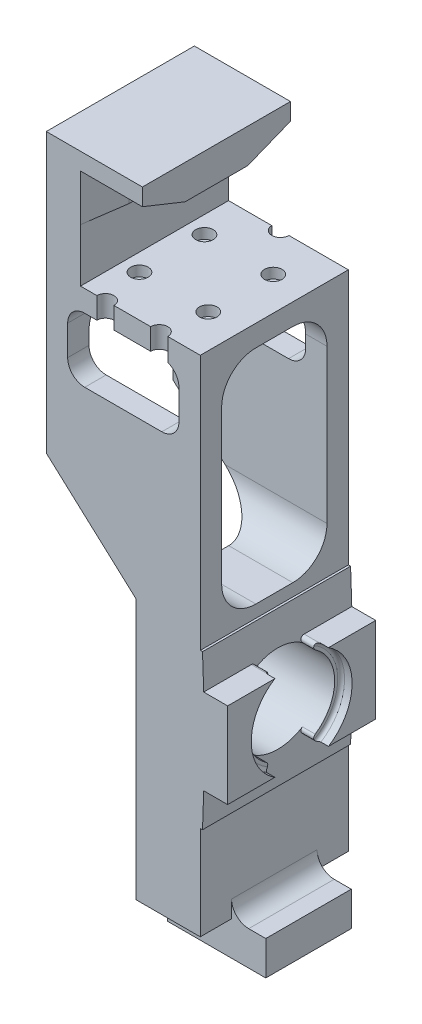
SolidWorks part; units mm, degrees
ref_plane "Front Plane" through (0, 0, 0) normal (0, 0, 1) x (1, 0, 0)
ref_plane "Top Plane" through (0, 0, 0) normal (0, 1, 0) x (1, 0, 0)
ref_plane "Right Plane" through (0, 0, 0) normal (1, 0, 0) x (0, 0, -1)
sketch "Sketch1" plane through (0, 0, 0) normal (0, 0, 1) x (1, 0, 0)
  line L0 (-19.75, 28.514) -> (-19.75, 29.784)
  line L1 (-12.7, 12.7) -> (12.7, 12.7)
  line L2 (-12.7, 12.7) -> (-12.7, -12.7)
  line L3 (-12.7, -12.7) -> (12.7, -12.7)
  line L4 (12.7, 12.7) -> (12.7, -12.7)
  line L5 (-12.7, 12.7) -> (12.7, -12.7) construction
  line L6 (-12.7, -12.7) -> (12.7, 12.7) construction
  line L7 (-21, 30.5968) -> (21, 30.5968)
  line L8 (-21, 30.5968) -> (-21, 29.784)
  line L9 (-21, 29.784) -> (21, 29.784)
  line L10 (21, 30.5968) -> (21, 29.784)
  line L11 (-21, 30.5968) -> (21, 29.784) construction
  line L12 (-21, 29.784) -> (21, 30.5968) construction
  line L13 (-21.6, 28.514) -> (-13.9, 28.514)
  line L14 (-21.6, 28.514) -> (-21.6, 24.714)
  line L15 (-21.6, 24.714) -> (-13.9, 24.714)
  line L16 (-13.9, 28.514) -> (-13.9, 24.714)
  line L17 (-21.6, 28.514) -> (-13.9, 24.714) construction
  line L18 (-21.6, 24.714) -> (-13.9, 28.514) construction
  line L19 (-15.75, 28.514) -> (-15.75, 29.784)
  line L20 (-19.75, 29.149) -> (-15.75, 29.149) construction
  line L21 (-19.75, 28.514) -> (-19.75, 20.514)
  line L22 (-15.75, 28.514) -> (-15.75, 20.514)
  point P0 (0, 0)
  point P6 (0, 30.1904)
  point P11 (-17.75, 26.614)
  point P22 (-17.75, 29.149)
  dimension "D1" = 25.4
  dimension "D2" = 25.4
  dimension "D3" = 0.8128
  dimension "D4" = 42
  dimension "D5" = 30.5968
  dimension "D6" = 3.8
  dimension "D7" = 7.7
  dimension "D8" = 4
  dimension "D9" = 1.25
  dimension "D10" = 1.27
  dimension "D11" = 4.2
sketch "Sketch2" plane through (0, 0, 0) normal (0, 0, 1) x (1, 0, 0)
  line L0 (-21.1524, 30.8508) -> (-17, 30.8508)
  line L1 (-12.7, -12.7) -> (-17.4625, -12.7)
  line L2 (-12.7, -12.7) -> (-12.7, 24.714)
  line L3 (-24.14, 12.7) -> (-17.4625, 6.6484)
  line L4 (-17.4625, -12.7) -> (-17.4625, 6.6484)
  line L5 (-17, 30.8508) -> (-17, 33.3908)
  line L6 (-17, 33.3908) -> (-24.14, 33.3908)
  line L7 (-24.14, 33.3908) -> (-24.14, 12.7)
  line L9 (-21.1524, 30.8508) -> (-21.1524, 28.6664)
  line L10 (-21, 30.5968) -> (-21, 29.784) construction
  line L12 (-21.1524, 28.6664) -> (-21.6, 28.6664)
  line L13 (-21.6, 28.6664) -> (-21.6, 24.714)
  line L14 (-21.6, 24.714) -> (-13.9, 24.714)
  line L15 (-12.7, 24.714) -> (-13.9, 24.714)
  line L17 (-12.7, 12.7) -> (12.7, 12.7) construction
  line L19 (-21, 30.5968) -> (21, 30.5968) construction
  line L20 (-21.6, 28.514) -> (-13.9, 28.514) construction
  dimension "D1" = 4.7625
  dimension "D2" = 0.254
  dimension "D3" = 0.1524
  dimension "D4" = 2.54
  dimension "D5" = 2.54
  dimension "D6" = 4
  dimension "D7" = 6.6484
  dimension "D8" = 0.1524
extrude "Boss-Extrude1" add sketch "Sketch2" along normal mid plane 11
sketch "Sketch28" [suppressed] plane through (0, 0, 5.5) normal (0, 0, 1) x (1, 0, 0)
  line L0 (-21.6, 28.7528) -> (-21.6, 24.9528) construction
  line L1 (-17, 33.6296) -> (-24.14, 33.6296) construction
  point P0 (-21.6, 32.3596)
  dimension "D1" = 1.27
sketch "Sketch30" [suppressed] plane through (-21.1524, 0, 0) normal (1, 0, 0) x (0, 0, -1)
  line L0 (-5.5, 31.0896) -> (5.5, 31.0896) construction
  line L1 (-5.5, 31.0896) -> (-5.5, 33.6296) construction
  point P0 (-2.325, 31.0896)
  dimension "D1" = 3.175
sketch3d "3DSketch1" [suppressed]
  line L0 (-21.6, 32.3596, 5.5) -> (-21.1524, 31.0896, 2.325)
sketch "Sketch15" plane through (0, 0, 5.5) normal (0, 0, 1) x (1, 0, 0)
  line L0 (-21.6, 28.6664) -> (-21.6, 28.3056)
  line L1 (-17, 33.3908) -> (-24.14, 33.3908) construction
  line L2 (-16.4004, 32.1208) -> (-21.6, 32.1208)
  line L3 (-21.6, 32.1208) -> (-21.6, 28.6664)
  line L4 (-21.6, 28.3056) -> (-16.4004, 28.3056)
  line L5 (-16.4004, 28.3056) -> (-16.4004, 32.1208)
  line L7 (-21.6, 28.514) -> (-21.6, 24.714) construction
  line L9 (-21.1524, 28.6664) -> (-21.6, 28.6664) construction
  line L10 (-16.4004, 32.1208) -> (-16.4004, 31.6732) construction
  dimension "D1" = 1.27
extrude "Cut-Extrude8" cut sketch "Sketch15" along direction (0.1298, -0.3682, -0.9206) on the side against the normal up to vertex (3.175 mm away) up to point (-21.1524, 31.0896, 2.325)
mirror "Mirror3" about plane through (0, 0, 0) normal (0, 0, 1) of "Cut-Extrude8"
sketch "Sketch4" plane through (0, 0, 0) normal (0, 0, 1) x (1, 0, 0)
  line L0 (-12.7, 12.7) -> (-12.7, -12.7) construction
  line L1 (-12.7, 3.175) -> (-10.668, 3.175)
  line L2 (-12.7, 3.175) -> (-12.7, -3.175)
  line L3 (-12.7, -3.175) -> (-10.668, -3.175)
  line L4 (-10.668, 3.175) -> (-10.668, -3.175)
  point P6 (-12.7, 0)
  dimension "D1" = 6.35
  dimension "D2" = 2.032
extrude "Boss-Extrude2" add sketch "Sketch4" along normal mid plane 11
sketch "Sketch10" plane through (0, 24.714, 0) normal (0, 1, 0) x (1, 0, 0)
  line L0 (-17, -5.5) -> (-24.14, -5.5) construction
  line L1 (-12.7, -5.5) -> (-21.6, -5.5) construction
  line L2 (-21.6, 0) -> (-13.9, 0) construction
  line L3 (-21.6, 0) -> (-13.9, 0) construction
  line L4 (-21.6, 0) -> (-13.9, 0) construction
  line L5 (-17, 5.5) -> (-24.14, 5.5) construction
  line L6 (-19.75, -5.5) -> (-15.75, -5.5) construction
  circle A0 centre (-19.75, -5.5) radius 0.635
  circle A1 centre (-15.75, -5.5) radius 0.635
  circle A2 centre (-17.75, 5.5) radius 0.635
  point P8 (-19.75, 0)
  point P9 (-15.75, 0)
  point P22 (-17.75, -5.5)
  dimension "D1" = 1.27
extrude "Cut-Extrude3" cut sketch "Sketch10" against normal up to vertex (4.2 mm away) up to point (-19.75, 20.514, 0)
sketch "Sketch11" plane through (0, 24.714, 0) normal (0, 1, 0) x (1, 0, 0)
  line L0 (-21.6, 0) -> (-13.9, 0) construction
  line L1 (-20.305, 2.415) -> (-15.195, 2.415) construction
  line L2 (-20.305, 2.415) -> (-20.305, -2.415) construction
  line L3 (-20.305, -2.415) -> (-15.195, -2.415) construction
  line L4 (-15.195, 2.415) -> (-15.195, -2.415) construction
  line L5 (-20.305, 2.415) -> (-15.195, -2.415) construction
  line L6 (-20.305, -2.415) -> (-15.195, 2.415) construction
  line L7 (-21.6, -5.5) -> (-21.6, 5.5) construction
  circle A0 centre (-20.305, 2.415) radius 0.65
  circle A1 centre (-15.195, 2.415) radius 0.65
  circle A2 centre (-15.195, -2.415) radius 0.65
  circle A3 centre (-20.305, -2.415) radius 0.65
  point P0 (-17.75, 0)
  dimension "D4" = 1.3
  dimension "D1" = 4.83
  dimension "D2" = 5.11
  dimension "D3" = 3.85
extrude "Cut-Extrude4" cut sketch "Sketch11" against normal blind 0.762
sketch "Sketch16" plane through (0, 0, 0) normal (0, 0, 1) x (1, 0, 0)
  line L5 (-22.5525, 23.1265) -> (-14.2875, 23.1265)
  line L6 (-14.2875, 23.1265) -> (-14.2875, 5.9135)
  line L7 (-22.5525, 33.3908) -> (-22.5525, 13.4037)
  line L8 (-22.5525, 13.4037) -> (-16.3965, 7.8248)
  line L9 (-22.5525, 23.1265) -> (-22.5525, 13.4037)
  line L10 (-22.5525, 13.4037) -> (-14.2875, 5.9135)
  line L12 (-12.7, 3.175) -> (-12.7, 24.714) construction
  line L13 (-21.6, 24.714) -> (-13.9, 24.714) construction
  dimension "D2" = 1.5875
  dimension "D3" = 1.5875
  dimension "D1" = 1.5875
extrude "Cut-Extrude9" [suppressed] cut sketch "Sketch16" against normal mid plane 13.462
fillet "Fillet5" [suppressed] radius 1.27
sketch "Sketch33" plane through (-17.4625, 0, 0) normal (-1, 0, 0) x (0, 0, 1)
  line L0 (5.5, -12.7) -> (-5.5, -12.7) construction
  line L1 (-3.175, -12.7) -> (3.175, -12.7)
  line L2 (-3.175, -12.7) -> (-3.175, -15.24)
  line L3 (-3.175, -15.24) -> (3.175, -15.24)
  line L4 (3.175, -12.7) -> (3.175, -15.24)
  point P6 (0, -12.7)
  dimension "D1" = 6.35
  dimension "D2" = 2.54
extrude "Boss-Extrude13" add sketch "Sketch33" against normal up to surface (4.7625 mm away) up to face at (-12.7, -10.3188, 1.375)
sketch "Sketch34" plane through (0, 0, 5.5) normal (0, 0, 1) x (1, 0, 0)
  line L0 (-12.6766, 9.7821) -> (-12.5571, 6.3592)
  line L1 (-12.5351, 5.7282) -> (-12.4853, 4.3048)
  line L2 (-10.2769, 4.382) -> (-10.3486, 6.4364)
  line L3 (-8.711, 7.1484) -> (-5.803, 4.2404)
  line L4 (-4.5085, 1.1153) -> (-4.5085, -1.1153)
  line L5 (-5.803, -4.2404) -> (-8.711, -7.1484)
  line L6 (-10.3486, -6.4364) -> (-10.2769, -4.382)
  line L7 (-12.4853, -4.3048) -> (-12.5351, -5.7282)
  line L8 (-12.5571, -6.3592) -> (-12.6766, -9.7821)
  line L9 (-9.7821, -12.6766) -> (-6.3592, -12.5571)
  line L10 (-5.7282, -12.5351) -> (-4.3048, -12.4853)
  line L11 (-4.382, -10.2769) -> (-6.4364, -10.3486)
  line L12 (-7.1484, -8.711) -> (-4.2404, -5.803)
  line L13 (-1.1153, -4.5085) -> (1.1153, -4.5085)
  line L14 (4.2404, -5.803) -> (7.1484, -8.711)
  line L15 (6.4364, -10.3486) -> (4.382, -10.2769)
  line L16 (4.3048, -12.4853) -> (5.7282, -12.5351)
  line L17 (6.3592, -12.5571) -> (9.7821, -12.6766)
  line L18 (12.6766, -9.7821) -> (12.5571, -6.3592)
  line L19 (12.5351, -5.7282) -> (12.4853, -4.3048)
  line L20 (10.2769, -4.382) -> (10.3486, -6.4364)
  line L21 (8.711, -7.1484) -> (5.803, -4.2404)
  line L22 (4.5085, -1.1153) -> (4.5085, 1.1153)
  line L23 (5.803, 4.2404) -> (8.711, 7.1484)
  line L24 (10.3486, 6.4364) -> (10.2769, 4.382)
  line L25 (12.4853, 4.3048) -> (12.5351, 5.7282)
  line L26 (12.5571, 6.3592) -> (12.6766, 9.7821)
  line L27 (9.7821, 12.6766) -> (6.3592, 12.5571)
  line L28 (5.7282, 12.5351) -> (4.3048, 12.4853)
  line L29 (4.382, 10.2769) -> (6.4364, 10.3486)
  line L30 (7.1484, 8.711) -> (4.2404, 5.803)
  line L31 (1.1153, 4.5085) -> (-1.1153, 4.5085)
  line L32 (-4.2404, 5.803) -> (-7.1484, 8.711)
  line L33 (-6.4364, 10.3486) -> (-4.382, 10.2769)
  line L34 (-4.3048, 12.4853) -> (-5.7282, 12.5351)
  line L35 (-6.3592, 12.5571) -> (-9.7821, 12.6766)
  arc A0 (-10.4131, 12.6987) -> (-12.6987, 10.4131) centre (-10.4902, 10.4902) ccw
  arc A1 (-12.6766, 9.7821) -> (-12.6987, 10.4131) centre (-12.6876, 10.0976) ccw
  arc A2 (-12.5351, 5.7282) -> (-12.5571, 6.3592) centre (-12.5461, 6.0437) ccw
  arc A3 (-12.4853, 4.3048) -> (-10.2769, 4.382) centre (-11.3811, 4.3434) ccw
  arc A4 (-8.711, 7.1484) -> (-10.3486, 6.4364) centre (-9.3896, 6.4698) ccw
  arc A5 (-4.5085, 1.1153) -> (-5.803, 4.2404) centre (-8.9281, 1.1153) ccw
  arc A6 (-5.803, -4.2404) -> (-4.5085, -1.1153) centre (-8.9281, -1.1153) ccw
  arc A7 (-10.3486, -6.4364) -> (-8.711, -7.1484) centre (-9.3896, -6.4698) ccw
  arc A8 (-10.2769, -4.382) -> (-12.4853, -4.3048) centre (-11.3811, -4.3434) ccw
  arc A9 (-12.5571, -6.3592) -> (-12.5351, -5.7282) centre (-12.5461, -6.0437) ccw
  arc A10 (-12.6987, -10.4131) -> (-12.6766, -9.7821) centre (-12.6876, -10.0976) ccw
  arc A11 (-12.6987, -10.4131) -> (-10.4131, -12.6987) centre (-10.4902, -10.4902) ccw
  arc A12 (-9.7821, -12.6766) -> (-10.4131, -12.6987) centre (-10.0976, -12.6876) ccw
  arc A13 (-5.7282, -12.5351) -> (-6.3592, -12.5571) centre (-6.0437, -12.5461) ccw
  arc A14 (-4.3048, -12.4853) -> (-4.382, -10.2769) centre (-4.3434, -11.3811) ccw
  arc A15 (-7.1484, -8.711) -> (-6.4364, -10.3486) centre (-6.4698, -9.3896) ccw
  arc A16 (-1.1153, -4.5085) -> (-4.2404, -5.803) centre (-1.1153, -8.9281) ccw
  arc A17 (4.2404, -5.803) -> (1.1153, -4.5085) centre (1.1153, -8.9281) ccw
  arc A18 (6.4364, -10.3486) -> (7.1484, -8.711) centre (6.4698, -9.3896) ccw
  arc A19 (4.382, -10.2769) -> (4.3048, -12.4853) centre (4.3434, -11.3811) ccw
  arc A20 (6.3592, -12.5571) -> (5.7282, -12.5351) centre (6.0437, -12.5461) ccw
  arc A21 (10.4131, -12.6987) -> (9.7821, -12.6766) centre (10.0976, -12.6876) ccw
  arc A22 (10.4131, -12.6987) -> (12.6987, -10.4131) centre (10.4902, -10.4902) ccw
  arc A23 (12.6766, -9.7821) -> (12.6987, -10.4131) centre (12.6876, -10.0976) ccw
  arc A24 (12.5351, -5.7282) -> (12.5571, -6.3592) centre (12.5461, -6.0437) ccw
  arc A25 (12.4853, -4.3048) -> (10.2769, -4.382) centre (11.3811, -4.3434) ccw
  arc A26 (8.711, -7.1484) -> (10.3486, -6.4364) centre (9.3896, -6.4698) ccw
  arc A27 (4.5085, -1.1153) -> (5.803, -4.2404) centre (8.9281, -1.1153) ccw
  arc A28 (5.803, 4.2404) -> (4.5085, 1.1153) centre (8.9281, 1.1153) ccw
  arc A29 (10.3486, 6.4364) -> (8.711, 7.1484) centre (9.3896, 6.4698) ccw
  arc A30 (10.2769, 4.382) -> (12.4853, 4.3048) centre (11.3811, 4.3434) ccw
  arc A31 (12.5571, 6.3592) -> (12.5351, 5.7282) centre (12.5461, 6.0437) ccw
  arc A32 (12.6987, 10.4131) -> (12.6766, 9.7821) centre (12.6876, 10.0976) ccw
  arc A33 (12.6987, 10.4131) -> (10.4131, 12.6987) centre (10.4902, 10.4902) ccw
  arc A34 (9.7821, 12.6766) -> (10.4131, 12.6987) centre (10.0976, 12.6876) ccw
  arc A35 (5.7282, 12.5351) -> (6.3592, 12.5571) centre (6.0437, 12.5461) ccw
  arc A36 (4.3048, 12.4853) -> (4.382, 10.2769) centre (4.3434, 11.3811) ccw
  arc A37 (7.1484, 8.711) -> (6.4364, 10.3486) centre (6.4698, 9.3896) ccw
  arc A38 (1.1153, 4.5085) -> (4.2404, 5.803) centre (1.1153, 8.9281) ccw
  arc A39 (-4.2404, 5.803) -> (-1.1153, 4.5085) centre (-1.1153, 8.9281) ccw
  arc A40 (-6.4364, 10.3486) -> (-7.1484, 8.711) centre (-6.4698, 9.3896) ccw
  arc A41 (-4.382, 10.2769) -> (-4.3048, 12.4853) centre (-4.3434, 11.3811) ccw
  arc A42 (-6.3592, 12.5571) -> (-5.7282, 12.5351) centre (-6.0437, 12.5461) ccw
  arc A43 (-10.4131, 12.6987) -> (-9.7821, 12.6766) centre (-10.0976, 12.6876) ccw
  point P124 (0, 0)
sketch "Sketch35" [suppressed] plane through (0, 0, 5.5) normal (0, 0, 1) x (1, 0, 0)
  line L0 (-12.6766, 9.7821) -> (-12.5571, 6.3592) construction
  line L1 (-12.5351, 5.7282) -> (-12.4459, 3.175)
  line L2 (-12.7, 5.7282) -> (-12.5351, 5.7282)
  line L3 (-10.668, 3.175) -> (-12.7, 3.175) construction
  line L4 (-12.4459, 3.175) -> (-12.7, 3.175)
  line L5 (-12.7, 3.175) -> (-12.7, 5.7282)
  line L6 (-12.7, 12.7) -> (-12.7, -12.7) construction
  line L7 (-10.668, 0) -> (-14.6378, 0) construction
  line L8 (-10.668, -3.175) -> (-10.668, 3.175) construction
  line L9 (-12.7, -3.175) -> (-12.7, -5.7282)
  line L10 (-12.4459, -3.175) -> (-12.7, -3.175)
  line L11 (-12.7, -5.7282) -> (-12.5351, -5.7282)
  line L12 (-12.5351, -5.7282) -> (-12.4459, -3.175)
extrude "Boss-Extrude16" [suppressed] add sketch "Sketch35" against normal up to surface (11 mm away) up to face at (-17.1127, 14.6311, -5.5)
sketch "Sketch17" plane through (0, 0, 0) normal (1, 0, 0) x (0, 0, -1)
  line L0 (5.9995, 20.4279) -> (5.9995, 17.6874)
  line L1 (8.2601, 24.0081) -> (29.53, 24.0081)
  line L2 (7.5006, 23.2486) -> (7.5006, 20.1861)
  line L3 (7.7495, 14.478) -> (30.0406, 14.478)
  line L4 (30.2895, 23.2486) -> (30.2895, 20.1861)
  line L5 (5.9995, 19.0576) -> (9.4881, 19.0576) construction
  line L6 (6.1793, 20.5473) -> (7.3208, 20.0667)
  line L7 (6.1793, 17.568) -> (7.3208, 18.0485)
  line L8 (18.8951, 24.0081) -> (18.8951, 14.478) construction
  line L11 (7.7495, 14.478) -> (30.0406, 14.478)
  line L12 (7.7495, 14.478) -> (7.7495, 14.1021)
  line L13 (7.7495, 14.1021) -> (30.0406, 14.1021)
  line L14 (30.0406, 14.478) -> (30.0406, 14.1021)
  line L18 (7.5006, 17.9291) -> (7.5006, 14.7269)
  line L19 (30.2895, 17.9291) -> (30.2895, 14.7269)
  line L25 (31.7906, 19.0576) -> (28.302, 19.0576) construction
  line L26 (31.6108, 17.568) -> (30.4693, 18.0485)
  line L27 (31.6108, 20.5473) -> (30.4693, 20.0667)
  line L42 (31.7906, 20.4279) -> (31.7906, 17.6874)
  arc A0 (30.0406, 14.478) -> (30.2895, 14.7269) centre (30.0406, 14.7269) ccw
  arc A1 (7.5006, 14.7269) -> (7.7495, 14.478) centre (7.7495, 14.7269) ccw
  arc A2 (8.2601, 24.0081) -> (7.5006, 23.2486) centre (8.2601, 23.2486) ccw
  arc A3 (29.53, 24.0081) -> (30.2895, 23.2486) centre (29.53, 23.2486) cw
  arc A4 (7.3208, 18.0485) -> (7.5006, 17.9291) centre (7.3711, 17.9291) cw
  arc A5 (5.9995, 17.6874) -> (6.1793, 17.568) centre (6.129, 17.6874) ccw
  arc A6 (5.9995, 20.4279) -> (6.1793, 20.5473) centre (6.129, 20.4279) cw
  arc A7 (7.3208, 20.0667) -> (7.5006, 20.1861) centre (7.3711, 20.1861) ccw
  arc A12 (30.4693, 20.0667) -> (30.2895, 20.1861) centre (30.419, 20.1861) cw
  arc A13 (31.7906, 20.4279) -> (31.6108, 20.5473) centre (31.6611, 20.4279) ccw
  arc A14 (31.7906, 17.6874) -> (31.6108, 17.568) centre (31.6611, 17.6874) cw
  arc A15 (30.4693, 18.0485) -> (30.2895, 17.9291) centre (30.419, 17.9291) ccw
  dimension "D9" = 0.7595
  dimension "D10" = 0.1295
  dimension "D11" = 0.2489
  dimension "D1" = 22.7889
  dimension "D2" = 9.5301
  dimension "D3" = 1.5011
  dimension "D4" = 7.5006
  dimension "D5" = 14.478
  dimension "D6" = 4.5796
  dimension "D7" = 67.17
  dimension "D8" = 1.4427
  dimension "D12" = 9.906
sketch "Sketch36" plane through (0, 0, 5.5) normal (0, 0, 1) x (1, 0, 0)
  line L0 (-12.5351, 5.7282) -> (-12.4459, 3.175)
  line L1 (-10.668, 3.175) -> (-12.7, 3.175) construction
  line L2 (-12.4459, 3.175) -> (-12.7, 3.175)
  line L3 (-12.7, 3.175) -> (-12.7, 5.7282)
  line L4 (-12.7, 12.7) -> (-12.7, -12.7) construction
  line L5 (-12.7, 5.7282) -> (-12.5351, 5.7282)
  line L6 (-12.5351, 5.7282) -> (-12.4853, 4.3048) construction
  line L7 (-10.668, 0) -> (-14.6943, 0) construction
  line L8 (-10.668, -3.175) -> (-10.668, 3.175) construction
  line L9 (-12.7, -5.7282) -> (-12.5351, -5.7282)
  line L10 (-12.7, -3.175) -> (-12.7, -5.7282)
  line L11 (-12.4459, -3.175) -> (-12.7, -3.175)
  line L12 (-12.5351, -5.7282) -> (-12.4459, -3.175)
extrude "Boss-Extrude17" add sketch "Sketch36" against normal up to surface (11 mm away) up to face at (-17.1127, 14.6311, -5.5)
sketch "Sketch27" plane through (0, 0, 0) normal (1, 0, 0) x (0, 0, -1)
  line L0 (-5.5, 5.7282) -> (-5.5, 24.714) construction
  line L1 (-3.9125, 23.1265) -> (3.9125, 23.1265)
  line L2 (-3.9125, 23.1265) -> (-3.9125, 6.6484)
  line L3 (-3.9125, 6.6484) -> (3.9125, 6.6484)
  line L4 (3.9125, 23.1265) -> (3.9125, 6.6484)
  line L5 (5.5, 24.714) -> (5.5, 28.6664) construction
  line L6 (-5.5, 24.714) -> (5.5, 24.714) construction
  line L8 (-5.5, 6.6484) -> (5.5, 6.6484) construction
  dimension "D1" = 1.5875
  dimension "D2" = 1.5875
  dimension "D3" = 1.5875
extrude "Cut-Extrude11" cut sketch "Sketch27" against normal up to surface (24.14 mm away) up to face at (-24.14, 23.0454, 0)
sketch "Sketch18" plane through (-12.7, 0, 0) normal (1, 0, 0) x (0, 0, -1)
  line L0 (5.5, 24.714) -> (5.5, 28.6664) construction
  line L1 (5.5, 24.0081) -> (33.3781, 24.0081)
  line L2 (5.5, 24.0081) -> (5.5, 14.1021)
  line L3 (5.5, 14.1021) -> (33.3781, 14.1021)
  line L4 (33.3781, 24.0081) -> (33.3781, 14.1021)
  line L5 (8.2601, 24.0081) -> (29.53, 24.0081) construction
  line L7 (31.7906, 20.4279) -> (31.7906, 17.6874) construction
  line L8 (7.7495, 14.1021) -> (30.0406, 14.1021) construction
  dimension "D1" = 1.5875
extrude "Boss-Extrude3" [suppressed] add sketch "Sketch18" along normal blind 1.27 from offset 4.4806 offset against normal yes
sketch "Sketch20" [suppressed] plane through (0, 14.1021, 0) normal (0, -1, 0) x (1, 0, 0)
  line L0 (-15.9106, -33.3781) -> (-17.1806, -33.3781) construction
  line L1 (-15.9106, -5.5) -> (-18.4506, -5.5)
  line L2 (-15.9106, -5.5) -> (-15.9106, -33.3781)
  line L3 (-15.9106, -33.3781) -> (-18.4506, -33.3781)
  line L4 (-18.4506, -5.5) -> (-18.4506, -33.3781)
  dimension "D1" = 2.54
extrude "Boss-Extrude5" [suppressed] add sketch "Sketch20" along normal blind 1.27
sketch "Sketch19" [suppressed] plane through (-17.1806, 0, 0) normal (-1, 0, 0) x (0, 0, 1)
  line L0 (-30.2895, 20.1861) -> (-30.2895, 24.0081)
  line L1 (-33.3781, 24.0081) -> (-5.5, 24.0081) construction
  line L2 (-30.2895, 17.9291) -> (-30.2895, 12.8321)
  line L4 (-30.2895, 12.8321) -> (-33.3781, 12.8321)
  line L5 (-33.3781, 12.8321) -> (-33.3781, 24.0081)
  line L6 (-33.3781, 24.0081) -> (-30.2895, 24.0081)
  line L7 (-31.6108, 20.5473) -> (-30.4693, 20.0667) construction
  line L8 (-31.7906, 20.4279) -> (-31.7906, 17.6874) construction
  line L9 (-31.6108, 17.568) -> (-30.4693, 18.0485) construction
  line L10 (-31.6108, 20.5473) -> (-30.4693, 20.0667)
  line L11 (-31.7906, 20.4279) -> (-31.7906, 17.6874)
  line L12 (-31.6108, 17.568) -> (-30.4693, 18.0485)
  line L13 (-18.8951, 24.0081) -> (-18.8951, 14.478) construction
  line L14 (-18.8951, 24.0081) -> (-18.8951, 14.478) construction
  line L15 (-6.1793, 17.568) -> (-7.3208, 18.0485)
  line L16 (-5.9995, 20.4279) -> (-5.9995, 17.6874)
  line L17 (-6.1793, 20.5473) -> (-7.3208, 20.0667)
  line L18 (-5.5, 24.0081) -> (-7.5006, 24.0081)
  line L19 (-5.5, 24.0081) -> (-5.5, 20.7528) construction
  line L20 (-7.5006, 12.8321) -> (-5.5, 12.8321)
  line L21 (-7.5006, 17.9291) -> (-7.5006, 12.8321)
  line L22 (-7.5006, 20.1861) -> (-7.5006, 24.0081)
  line L23 (-5.5, 24.0081) -> (-5.5, 12.8321)
  arc A0 (-30.4693, 20.0667) -> (-30.2895, 20.1861) centre (-30.419, 20.1861) ccw construction
  arc A1 (-31.6108, 20.5473) -> (-31.7906, 20.4279) centre (-31.6611, 20.4279) ccw construction
  arc A2 (-31.7906, 17.6874) -> (-31.6108, 17.568) centre (-31.6611, 17.6874) ccw construction
  arc A3 (-30.2895, 17.9291) -> (-30.4693, 18.0485) centre (-30.419, 17.9291) ccw construction
  arc A4 (-30.4693, 20.0667) -> (-30.2895, 20.1861) centre (-30.419, 20.1861) ccw
  arc A5 (-31.6108, 20.5473) -> (-31.7906, 20.4279) centre (-31.6611, 20.4279) ccw
  arc A6 (-31.7906, 17.6874) -> (-31.6108, 17.568) centre (-31.6611, 17.6874) ccw
  arc A7 (-30.2895, 17.9291) -> (-30.4693, 18.0485) centre (-30.419, 17.9291) ccw
  arc A8 (-7.5006, 17.9291) -> (-7.3208, 18.0485) centre (-7.3711, 17.9291) cw
  arc A9 (-5.9995, 17.6874) -> (-6.1793, 17.568) centre (-6.129, 17.6874) cw
  arc A10 (-6.1793, 20.5473) -> (-5.9995, 20.4279) centre (-6.129, 20.4279) cw
  arc A11 (-7.3208, 20.0667) -> (-7.5006, 20.1861) centre (-7.3711, 20.1861) cw
extrude "Boss-Extrude4" [suppressed] add sketch "Sketch19" along normal blind 6.096
sketch "Sketch21" [suppressed] plane through (-15.9106, 0, 0) normal (1, 0, 0) x (0, 0, -1)
  line L4 (5.5, 24.0081) -> (5.5, 12.8321)
  line L5 (5.5, 12.8321) -> (33.3781, 12.8321)
  line L6 (33.3781, 12.8321) -> (33.3781, 24.0081)
  line L7 (33.3781, 24.0081) -> (5.5, 24.0081)
  line L8 (5.5, 24.0081) -> (5.5, 12.8321)
  line L9 (5.5, 12.8321) -> (33.3781, 12.8321)
  line L10 (33.3781, 12.8321) -> (33.3781, 24.0081)
  line L11 (33.3781, 24.0081) -> (5.5, 24.0081)
  dimension "D1" = 0
extrude "Boss-Extrude6" [suppressed] add sketch "Sketch21" along normal up to surface (3.2106 mm away) up to face at (-12.7, 14.8875, 0)
sketch "Sketch22" [suppressed] plane through (-23.2766, 0, 0) normal (-1, 0, 0) x (0, 0, 1)
  line L0 (-7.5006, 17.9291) -> (-7.5006, 12.8321) construction
  line L1 (-7.5006, 12.8321) -> (-5.5, 12.8321) construction
  line L2 (-5.5, 12.8321) -> (-5.5, 24.0081) construction
  line L3 (-5.5, 24.0081) -> (-7.5006, 24.0081) construction
  line L4 (-7.5006, 24.0081) -> (-7.5006, 20.1861) construction
  line L5 (-7.3208, 20.0667) -> (-6.1793, 20.5473) construction
  line L6 (-5.9995, 20.4279) -> (-5.9995, 17.6874) construction
  line L7 (-6.1793, 17.568) -> (-7.3208, 18.0485) construction
  line L8 (-30.2895, 20.1861) -> (-30.2895, 24.0081) construction
  line L9 (-30.2895, 24.0081) -> (-33.3781, 24.0081) construction
  line L10 (-33.3781, 24.0081) -> (-33.3781, 12.8321) construction
  line L11 (-33.3781, 12.8321) -> (-30.2895, 12.8321) construction
  line L12 (-30.2895, 12.8321) -> (-30.2895, 17.9291) construction
  line L13 (-30.4693, 18.0485) -> (-31.6108, 17.568) construction
  line L14 (-31.7906, 17.6874) -> (-31.7906, 20.4279) construction
  line L15 (-31.6108, 20.5473) -> (-30.4693, 20.0667) construction
  line L16 (-7.5006, 17.9291) -> (-7.5006, 12.8321)
  line L17 (-7.5006, 12.8321) -> (-5.5, 12.8321)
  line L18 (-5.5, 12.8321) -> (-5.5, 24.0081)
  line L19 (-5.5, 24.0081) -> (-7.5006, 24.0081)
  line L20 (-7.5006, 24.0081) -> (-7.5006, 20.1861)
  line L21 (-7.3208, 20.0667) -> (-6.1793, 20.5473)
  line L22 (-5.9995, 20.4279) -> (-5.9995, 17.6874)
  line L23 (-6.1793, 17.568) -> (-7.3208, 18.0485)
  line L24 (-30.2895, 20.1861) -> (-30.2895, 24.0081)
  line L25 (-30.2895, 24.0081) -> (-33.3781, 24.0081)
  line L26 (-33.3781, 24.0081) -> (-33.3781, 12.8321)
  line L27 (-33.3781, 12.8321) -> (-30.2895, 12.8321)
  line L28 (-30.2895, 12.8321) -> (-30.2895, 17.9291)
  line L29 (-30.4693, 18.0485) -> (-31.6108, 17.568)
  line L30 (-31.7906, 17.6874) -> (-31.7906, 20.4279)
  line L31 (-31.6108, 20.5473) -> (-30.4693, 20.0667)
  arc A0 (-7.3208, 18.0485) -> (-7.5006, 17.9291) centre (-7.3711, 17.9291) ccw construction
  arc A1 (-7.5006, 20.1861) -> (-7.3208, 20.0667) centre (-7.3711, 20.1861) ccw construction
  arc A2 (-5.9995, 20.4279) -> (-6.1793, 20.5473) centre (-6.129, 20.4279) ccw construction
  arc A3 (-6.1793, 17.568) -> (-5.9995, 17.6874) centre (-6.129, 17.6874) ccw construction
  arc A4 (-30.4693, 20.0667) -> (-30.2895, 20.1861) centre (-30.419, 20.1861) ccw construction
  arc A5 (-30.2895, 17.9291) -> (-30.4693, 18.0485) centre (-30.419, 17.9291) ccw construction
  arc A6 (-31.7906, 17.6874) -> (-31.6108, 17.568) centre (-31.6611, 17.6874) ccw construction
  arc A7 (-31.6108, 20.5473) -> (-31.7906, 20.4279) centre (-31.6611, 20.4279) ccw construction
  arc A8 (-7.3208, 18.0485) -> (-7.5006, 17.9291) centre (-7.3711, 17.9291) ccw
  arc A9 (-7.5006, 20.1861) -> (-7.3208, 20.0667) centre (-7.3711, 20.1861) ccw
  arc A10 (-5.9995, 20.4279) -> (-6.1793, 20.5473) centre (-6.129, 20.4279) ccw
  arc A11 (-6.1793, 17.568) -> (-5.9995, 17.6874) centre (-6.129, 17.6874) ccw
  arc A12 (-30.4693, 20.0667) -> (-30.2895, 20.1861) centre (-30.419, 20.1861) ccw
  arc A13 (-30.2895, 17.9291) -> (-30.4693, 18.0485) centre (-30.419, 17.9291) ccw
  arc A14 (-31.7906, 17.6874) -> (-31.6108, 17.568) centre (-31.6611, 17.6874) ccw
  arc A15 (-31.6108, 20.5473) -> (-31.7906, 20.4279) centre (-31.6611, 20.4279) ccw
extrude "Boss-Extrude7" [suppressed] add sketch "Sketch22" along normal up to surface (0.8634 mm away) up to face at (-24.14, 20.4793, 0)
sketch "Sketch23" plane through (0, 0, -5.5) normal (0, 0, -1) x (-1, 0, 0)
  line L10 (24.14, 12.7) -> (24.14, 33.3908)
  line L11 (17.115, 20.514) -> (17.115, 24.714)
  line L12 (17.115, 20.514) -> (17.115, 24.714)
  line L13 (12.4459, 3.175) -> (10.668, 3.175)
  line L14 (10.668, 3.175) -> (10.668, -3.175)
  line L15 (10.668, -3.175) -> (12.4459, -3.175)
  line L16 (12.7, -5.7282) -> (12.7, -12.7)
  line L17 (12.7, -12.7) -> (17.4625, -12.7)
  line L18 (17.4625, -12.7) -> (17.4625, 6.6484)
  line L19 (17.4625, 6.6484) -> (24.14, 12.7)
  line L20 (24.14, 12.7) -> (24.14, 33.3908)
  line L23 (12.4459, 3.175) -> (10.668, 3.175)
  line L24 (10.668, 3.175) -> (10.668, -3.175)
  line L25 (10.668, -3.175) -> (12.4459, -3.175)
  line L26 (12.7, -5.7282) -> (12.7, -12.7)
  line L27 (12.7, -12.7) -> (17.4625, -12.7)
  line L28 (17.4625, -12.7) -> (17.4625, 6.6484)
  line L29 (17.4625, 6.6484) -> (24.14, 12.7)
  line L32 (17.115, 24.714) -> (12.7, 24.714)
  line L33 (17.115, 24.714) -> (12.7, 24.714)
  line L34 (12.7, 24.714) -> (12.7, 5.7282)
  line L35 (12.7, 24.714) -> (12.7, 5.7282)
  line L36 (24.14, 33.3908) -> (17, 33.3908)
  line L37 (24.14, 33.3908) -> (17, 33.3908)
  line L38 (17, 33.3908) -> (17, 32.1208)
  line L39 (17, 33.3908) -> (17, 32.1208)
  line L40 (17, 32.1208) -> (21.6, 32.1208)
  line L41 (17, 32.1208) -> (21.6, 32.1208)
  line L51 (21.6, 32.1208) -> (21.6, 28.6664)
  line L52 (21.6, 32.1208) -> (21.6, 28.6664)
  line L53 (21.6, 28.6664) -> (21.6, 24.714)
  line L54 (21.6, 28.6664) -> (21.6, 24.714)
  line L55 (21.6, 24.714) -> (18.385, 24.714)
  line L56 (21.6, 24.714) -> (18.385, 24.714)
  line L57 (18.385, 24.714) -> (18.385, 20.514)
  line L58 (18.385, 24.714) -> (18.385, 20.514)
  line L59 (18.385, 20.514) -> (17.115, 20.514)
  line L60 (18.385, 20.514) -> (17.115, 20.514)
  line L61 (12.7, 5.7282) -> (12.5351, 5.7282)
  line L62 (12.7, 5.7282) -> (12.5351, 5.7282)
  line L63 (12.5351, 5.7282) -> (12.4459, 3.175)
  line L64 (12.5351, 5.7282) -> (12.4459, 3.175)
  line L65 (12.4459, -3.175) -> (12.5351, -5.7282)
  line L66 (12.4459, -3.175) -> (12.5351, -5.7282)
  line L67 (12.5351, -5.7282) -> (12.7, -5.7282)
  line L68 (12.5351, -5.7282) -> (12.7, -5.7282)
  dimension "D1" = 0
extrude "Boss-Extrude9" [suppressed] add sketch "Sketch23" along normal up to surface (2.0006 mm away)
sketch "Sketch24" [suppressed] plane through (0, 0, -7.5006) normal (0, 0, -1) x (-1, 0, 0)
  line L0 (18.4506, 12.8321) -> (18.4506, 7.5439)
  line L14 (17.1806, 14.1021) -> (18.4506, 14.1021)
  line L15 (18.4506, 14.1021) -> (18.4506, 12.8321)
  line L16 (18.4506, 12.8321) -> (12.7, 12.8321)
  line L17 (12.7, 12.8321) -> (12.7, 5.7282)
  line L18 (12.4459, 3.175) -> (10.668, 3.175)
  line L19 (10.668, 3.175) -> (10.668, -3.175)
  line L20 (10.668, -3.175) -> (12.4459, -3.175)
  line L21 (12.7, -5.7282) -> (12.7, -12.7)
  line L22 (12.7, -12.7) -> (17.4625, -12.7)
  line L23 (17.4625, -12.7) -> (17.4625, 6.6484)
  line L24 (17.4625, 6.6484) -> (24.14, 12.7)
  line L25 (24.14, 12.7) -> (24.14, 17.9291)
  line L26 (24.14, 17.9291) -> (17.1806, 17.9291)
  line L27 (17.1806, 17.9291) -> (17.1806, 14.1021)
  line L30 (18.4506, 12.8321) -> (12.7, 12.8321)
  line L31 (12.7, 12.8321) -> (12.7, 5.7282)
  line L32 (12.4459, 3.175) -> (10.668, 3.175)
  line L33 (10.668, 3.175) -> (10.668, -3.175)
  line L34 (10.668, -3.175) -> (12.4459, -3.175)
  line L35 (12.7, -5.7282) -> (12.7, -12.7)
  line L36 (12.7, -12.7) -> (17.4625, -12.7)
  line L37 (17.4625, -12.7) -> (17.4625, 6.6484)
  line L38 (17.4625, 6.6484) -> (18.4506, 7.5439)
  line L42 (12.7, 5.7282) -> (12.5351, 5.7282)
  line L43 (12.7, 5.7282) -> (12.5351, 5.7282)
  line L44 (12.5351, 5.7282) -> (12.4459, 3.175)
  line L45 (12.5351, 5.7282) -> (12.4459, 3.175)
  line L46 (12.4459, -3.175) -> (12.5351, -5.7282)
  line L47 (12.4459, -3.175) -> (12.5351, -5.7282)
  line L48 (12.5351, -5.7282) -> (12.7, -5.7282)
  line L49 (12.5351, -5.7282) -> (12.7, -5.7282)
  dimension "D1" = 0
sketch "Sketch25" [suppressed] plane through (0, 0, -33.3781) normal (0, 0, -1) x (-1, 0, 0)
  line L0 (24.14, 12.8321) -> (12.7, 12.8321) construction
  line L1 (24.14, 12.8321) -> (24.14, 24.0081) construction
  line L3 (24.14, 12.8321) -> (24.14, 12.7)
  line L14 (17.1806, 14.1021) -> (18.4506, 14.1021)
  line L15 (18.4506, 14.1021) -> (18.4506, 12.8321)
  line L16 (18.4506, 12.8321) -> (12.7, 12.8321)
  line L24 (12.7, 12.8321) -> (12.7, 5.7282)
  line L25 (24.14, 12.7) -> (24.14, 17.9291)
  line L26 (24.14, 17.9291) -> (17.1806, 17.9291)
  line L27 (17.1806, 17.9291) -> (17.1806, 14.1021)
  line L28 (12.7, 12.8321) -> (12.7, 5.7282)
  line L29 (12.4459, 3.175) -> (10.668, 3.175)
  line L31 (12.4459, 3.175) -> (10.668, 3.175)
  line L32 (10.668, 3.175) -> (10.668, -3.175)
  line L33 (10.668, 3.175) -> (10.668, -3.175)
  line L34 (10.668, -3.175) -> (12.4459, -3.175)
  line L35 (10.668, -3.175) -> (12.4459, -3.175)
  line L36 (12.7, -5.7282) -> (12.7, -12.7)
  line L37 (12.7, -5.7282) -> (12.7, -12.7)
  line L38 (12.7, -12.7) -> (17.4625, -12.7)
  line L39 (12.7, -12.7) -> (17.4625, -12.7)
  line L40 (17.4625, -12.7) -> (17.4625, 6.6484)
  line L41 (17.4625, -12.7) -> (17.4625, 6.6484)
  line L42 (17.4625, 6.6484) -> (24.14, 12.7)
  line L43 (17.4625, 6.6484) -> (24.14, 12.7)
  line L44 (12.7, 5.7282) -> (12.5351, 5.7282)
  line L45 (12.7, 5.7282) -> (12.5351, 5.7282)
  line L46 (12.5351, 5.7282) -> (12.4459, 3.175)
  line L47 (12.5351, 5.7282) -> (12.4459, 3.175)
  line L48 (12.4459, -3.175) -> (12.5351, -5.7282)
  line L49 (12.4459, -3.175) -> (12.5351, -5.7282)
  line L50 (12.5351, -5.7282) -> (12.7, -5.7282)
  line L51 (12.5351, -5.7282) -> (12.7, -5.7282)
  dimension "D1" = 0
extrude "Boss-Extrude11" [suppressed] add sketch "Sketch25" against normal up to surface (3.0886 mm away)
extrude "Boss-Extrude12" [suppressed] add sketch "Sketch24" along normal up to surface (22.7889 mm away)
ref_plane "Plane1" [suppressed] through (0, 0, -13.9391) normal (0, 0, 1) x (1, 0, 0)
sketch "Sketch5" plane through (-10.668, 0, 0) normal (1, 0, 0) x (0, 0, -1)
  circle A0 centre (0, 0) radius 3.7465
  dimension "D1" = 7.493
extrude "Cut-Extrude2" cut sketch "Sketch5" against normal blind 0.8128
hole_wizard "1/4 Clearance Hole1" positions "Sketch8" profile "Sketch7" hole size "1/4" standard "ANSI Inch"
sketch "Sketch8" plane through (-11.4808, 0, 0) normal (1, 0, 0) x (0, 0, -1)
  line L1 (13.9446, -12.7) -> (13.9446, 3.2006) construction
  point P0 (0, 0)
  point P4 (27.8892, 0)
  dimension "D1" = 27.8892
sketch "Sketch7" plane through (-11.4808, 0, 0) normal (0, 1, 0) x (0, 0, -1)
  line L0 (0, 0) -> (0, 8.3111)
  line L1 (0, 8.3111) -> (3.2639, 6.35)
  line L2 (3.2639, 6.35) -> (3.2639, 0)
  line L5 (3.2639, 0) -> (0, 0)
  line L10 (0, 8.3111) -> (-3.2639, 6.35) construction
  line L11 (0, -6.35) -> (0, 107.95) construction
  dimension "Hole Dia." = 6.5278
  dimension "Hole Depth" = 6.35
  dimension "Drill Angle" = 118
mirror "Mirror6" [suppressed] about plane through (0, 0, -13.9391) normal (0, 0, 1)
fillet "Fillet2" radius 0.254 2 edges at (-11.4808, 0, -3.7465) (-11.4808, 0, 3.7465)
fillet "Fillet12" radius 0.254 4 edges at (-11.9633, -3.175, -0.7566) (-11.9633, -3.175, 0.7566) (-11.9633, 3.175, -0.7566) (-11.9633, 3.175, 0.7566)
sketch "Sketch26" plane through (0, 0, 0) normal (1, 0, 0) x (0, 0, -1)
  line L0 (13.9446, -12.7) -> (13.9446, -11.1125) construction
  line L1 (28.4201, 22.4206) -> (9.3701, 22.4206)
  line L2 (28.4201, 22.4206) -> (28.4201, 6.6484)
  line L3 (28.4201, 6.6484) -> (22.8346, 6.6484)
  line L4 (9.3701, 22.4206) -> (9.3701, 6.6484)
  line L5 (9.3701, 6.6484) -> (5.0546, 6.6484)
  line L6 (22.8346, 6.6484) -> (22.8346, -11.1125)
  line L7 (22.8346, -11.1125) -> (5.0546, -11.1125)
  line L8 (5.0546, 6.6484) -> (5.0546, -11.1125)
  line L9 (-5.5, -12.7) -> (-3.175, -12.7) construction
  line L10 (-5.5, 6.6484) -> (-3.9125, 6.6484) construction
  line L11 (8.2601, 24.0081) -> (29.53, 24.0081) construction
  line L13 (3.175, -12.7) -> (5.5, -12.7) construction
  line L14 (0, 0) -> (27.8892, 0) construction
  line L15 (0, -12.7) -> (0, 12.7) construction
  point P8 (18.8951, 22.4206)
  point P25 (13.9446, 0)
  dimension "D1" = 19.05
  dimension "D2" = 17.78
  dimension "D3" = 1.5875
  dimension "D4" = 1.5875
extrude "Cut-Extrude10" [suppressed] cut sketch "Sketch26" against normal up to surface (18.4506 mm away)
fillet "Fillet6" [suppressed] radius 2.54
fillet "Fillet7" radius 2.54 4 edges at (-15.0812, 6.6484, -3.9125) (-15.0812, 6.6484, 3.9125) (-18.42, 23.1265, 3.9125) (-18.42, 23.1265, -3.9125)
fillet "Fillet8" [suppressed] radius 1.27
sketch "Sketch31" plane through (0, 0, 5.5) normal (0, 0, 1) x (1, 0, 0)
  line L0 (-22.5525, 23.1265) -> (-22.5525, 18.364)
  line L1 (-22.5525, 18.364) -> (-14.2875, 18.364)
  line L2 (-12.7, 24.714) -> (-15.115, 24.714) construction
  line L3 (-14.2875, 18.364) -> (-14.2875, 23.1265)
  line L4 (-14.2875, 23.1265) -> (-22.5525, 23.1265)
  line L6 (-24.14, 33.3908) -> (-24.14, 12.7) construction
  line L7 (-12.7, 5.7282) -> (-12.7, 24.714) construction
  dimension "D1" = 4.7625
  dimension "D2" = 1.5875
  dimension "D3" = 1.5875
  dimension "D4" = 1.5875
extrude "Cut-Extrude12" cut sketch "Sketch31" against normal blind 11.176
sketch "Sketch32" [suppressed] plane through (0, 0, -7.5006) normal (0, 0, -1) x (-1, 0, 0)
  line L0 (24.14, 24.0081) -> (17.1806, 24.0081) construction
  line L1 (17.1806, 24.0081) -> (19.75, 24.0081)
  line L2 (17.1806, 24.0081) -> (17.1806, 20.514)
  line L3 (17.1806, 20.514) -> (19.75, 20.514)
  line L4 (19.75, 24.0081) -> (19.75, 20.514)
  line L5 (17.1806, 20.1861) -> (17.1806, 24.0081) construction
  line L6 (12.7, 24.0081) -> (24.14, 24.0081) construction
extrude "Cut-Extrude13" [suppressed] cut sketch "Sketch32" against normal up to vertex contours L4 L3 L2 L1 up to point (-18.42, 23.1265, -1.3725)
fillet "Fillet13" [suppressed] radius 0.254
fillet "Fillet11" [suppressed] radius 0.254
fillet "Fillet14" radius 1.27 4 edges at (-22.5525, 18.364, 4.7062) (-14.2875, 18.364, 4.7062) (-14.2875, 23.1265, 3.4362) (-22.5525, 23.1265, 3.4362)
fillet "Fillet15" radius 1.27 4 edges at (-22.5525, 23.1265, -3.4362) (-14.2875, 23.1265, -3.4362) (-14.2875, 18.364, -4.7062) (-22.5525, 18.364, -4.7062)
sketch "Sketch37" [suppressed] plane through (-17.1806, 0, 0) normal (-1, 0, 0) x (0, 0, 1)
  line L0 (-30.2895, 18.0587) -> (-30.419, 18.0587)
  line L1 (-30.0355, 19.8026) -> (-30.0355, 18.3127)
  line L2 (-7.5006, 20.0566) -> (-7.3711, 20.0566)
  line L3 (-7.5006, 18.0587) -> (-7.3711, 18.0587)
  line L4 (-7.7546, 19.8026) -> (-7.7546, 18.3127)
  line L6 (-30.2895, 20.0566) -> (-30.419, 20.0566)
  line L8 (-30.2895, 20.1861) -> (-30.2895, 24.0081)
  line L9 (-30.2895, 24.0081) -> (-33.3781, 24.0081)
  line L10 (-33.3781, 24.0081) -> (-33.3781, 12.7)
  line L11 (-33.3781, 12.7) -> (-30.2895, 12.7)
  line L12 (-30.2895, 12.7) -> (-30.2895, 17.9291)
  line L13 (-30.4693, 18.0485) -> (-31.6108, 17.568)
  line L14 (-31.7906, 17.6874) -> (-31.7906, 20.4279)
  line L15 (-31.6108, 20.5473) -> (-30.4693, 20.0667)
  line L21 (-30.4693, 18.0485) -> (-31.6108, 17.568)
  line L22 (-31.7906, 17.6874) -> (-31.7906, 20.4279)
  line L23 (-31.6108, 20.5473) -> (-30.4693, 20.0667)
  line L30 (-7.5006, 17.9291) -> (-7.5006, 12.7)
  line L31 (-7.5006, 12.7) -> (-3.9125, 12.7)
  line L32 (-3.9125, 12.7) -> (-3.9125, 20.5865)
  line L33 (-1.3725, 23.1265) -> (1.3725, 23.1265)
  line L34 (3.9125, 20.5865) -> (3.9125, 12.7)
  line L35 (3.9125, 12.7) -> (5.5, 12.7)
  line L36 (5.5, 12.7) -> (5.5, 33.3908)
  line L37 (5.5, 33.3908) -> (-5.5, 33.3908)
  line L38 (-5.5, 33.3908) -> (-5.5, 24.0081)
  line L39 (-5.5, 24.0081) -> (-7.5006, 24.0081)
  line L40 (-7.5006, 24.0081) -> (-7.5006, 20.1861)
  line L41 (-7.3208, 20.0667) -> (-6.1793, 20.5473)
  line L42 (-5.9995, 20.4279) -> (-5.9995, 17.6874)
  line L43 (-6.1793, 17.568) -> (-7.3208, 18.0485)
  line L55 (-7.3208, 20.0667) -> (-6.1793, 20.5473)
  line L56 (-5.9995, 20.4279) -> (-5.9995, 17.6874)
  line L57 (-6.1793, 17.568) -> (-7.3208, 18.0485)
  arc A0 (-30.4693, 20.0667) -> (-30.2895, 20.1861) centre (-30.419, 20.1861) ccw construction
  arc A1 (-7.5006, 20.1861) -> (-7.3208, 20.0667) centre (-7.3711, 20.1861) ccw construction
  arc A2 (-7.5006, 18.0587) -> (-7.7546, 18.3127) centre (-7.5006, 18.3127) cw
  arc A3 (-7.5006, 20.0566) -> (-7.7546, 19.8026) centre (-7.5006, 19.8026) ccw
  arc A4 (-30.2895, 17.9291) -> (-30.4693, 18.0485) centre (-30.419, 17.9291) ccw
  arc A5 (-31.7906, 17.6874) -> (-31.6108, 17.568) centre (-31.6611, 17.6874) ccw
  arc A6 (-31.6108, 20.5473) -> (-31.7906, 20.4279) centre (-31.6611, 20.4279) ccw
  arc A7 (-30.4693, 20.0667) -> (-30.2895, 20.1861) centre (-30.419, 20.1861) ccw
  arc A8 (-30.419, 18.0587) -> (-30.4693, 18.0485) centre (-30.419, 17.9291) ccw
  arc A9 (-31.7906, 17.6874) -> (-31.6108, 17.568) centre (-31.6611, 17.6874) ccw
  arc A10 (-31.6108, 20.5473) -> (-31.7906, 20.4279) centre (-31.6611, 20.4279) ccw
  arc A11 (-30.4693, 20.0667) -> (-30.419, 20.0566) centre (-30.419, 20.1861) ccw
  arc A12 (-30.2895, 18.0587) -> (-30.0355, 18.3127) centre (-30.2895, 18.3127) ccw
  arc A13 (-30.2895, 20.0566) -> (-30.0355, 19.8026) centre (-30.2895, 19.8026) cw
  arc A14 (-1.3725, 23.1265) -> (-3.9125, 20.5865) centre (-1.3725, 20.5865) ccw
  arc A15 (3.9125, 20.5865) -> (1.3725, 23.1265) centre (1.3725, 20.5865) ccw
  arc A16 (-7.5006, 20.1861) -> (-7.3208, 20.0667) centre (-7.3711, 20.1861) ccw
  arc A17 (-5.9995, 20.4279) -> (-6.1793, 20.5473) centre (-6.129, 20.4279) ccw
  arc A18 (-6.1793, 17.568) -> (-5.9995, 17.6874) centre (-6.129, 17.6874) ccw
  arc A19 (-7.3208, 18.0485) -> (-7.5006, 17.9291) centre (-7.3711, 17.9291) ccw
  arc A22 (-7.3711, 20.0566) -> (-7.3208, 20.0667) centre (-7.3711, 20.1861) ccw
  arc A23 (-5.9995, 20.4279) -> (-6.1793, 20.5473) centre (-6.129, 20.4279) ccw
  arc A24 (-6.1793, 17.568) -> (-5.9995, 17.6874) centre (-6.129, 17.6874) ccw
  arc A25 (-7.3208, 18.0485) -> (-7.3711, 18.0587) centre (-7.3711, 17.9291) ccw
  dimension "D5" = 0.254
  dimension "D3" = 0.254
  dimension "D4" = 0.254
  dimension "D1" = 0
  dimension "D2" = 0
extrude "Cut-Extrude14" [suppressed] cut sketch "Sketch37" against normal up to next
sketch "Sketch38" plane through (-12.7, 0, 0) normal (1, 0, 0) x (0, 0, -1)
  line L1 (-3.175, -15.24) -> (3.175, -15.24)
  line L2 (-3.175, -15.24) -> (-3.175, -12.7)
  line L3 (-3.175, -12.7) -> (3.175, -12.7)
  line L4 (3.175, -15.24) -> (3.175, -12.7)
extrude "Boss-Extrude18" add sketch "Sketch38" along normal blind 2.54
fillet "Fillet16" radius 1.27 1 edges
